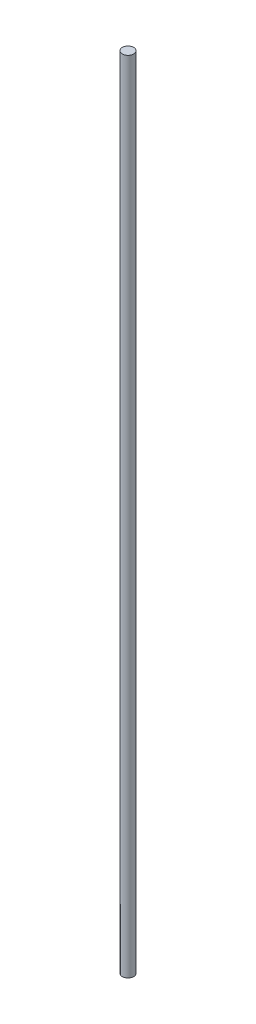
SolidWorks part; units mm, degrees
ref_plane "前基準面" through (0, 0, 0) normal (0, 0, 1) x (1, 0, 0)
ref_plane "上基準面" through (0, 0, 0) normal (0, 1, 0) x (1, 0, 0)
ref_plane "右基準面" through (0, 0, 0) normal (1, 0, 0) x (0, 0, -1)
sketch "草圖1" plane through (0, 0, 0) normal (0, 1, 0) x (1, 0, 0)
  circle A0 centre (0, 0) radius 2.5
  dimension "D1" = 5
extrude "填料-伸長1" add sketch "草圖1" along normal blind 350
